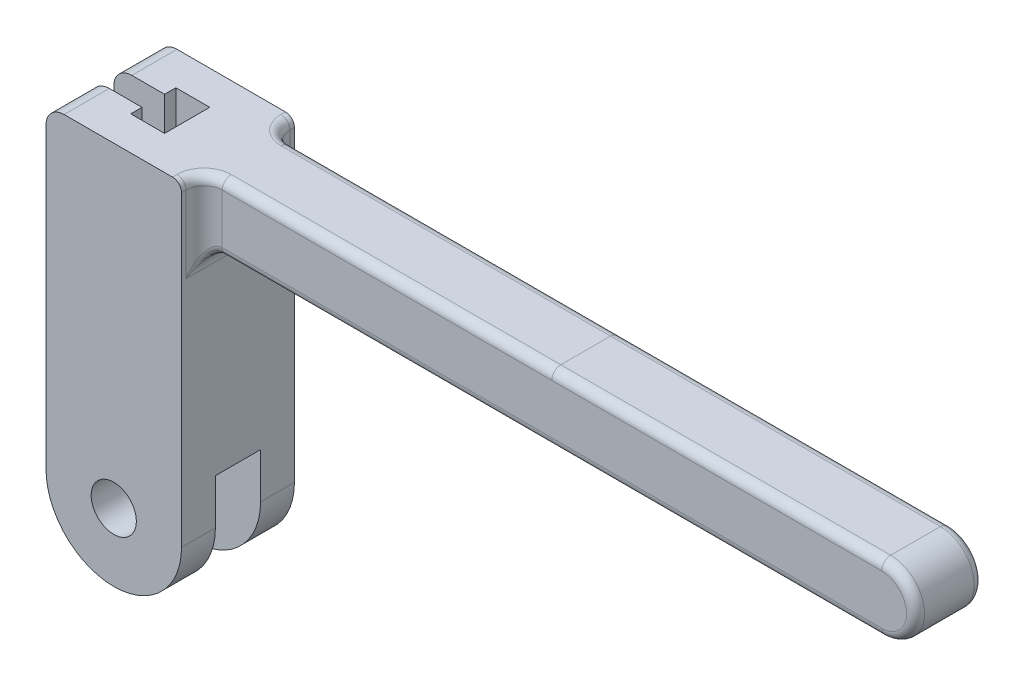
SolidWorks part; units mm, degrees
ref_plane "Front" through (0, 0, 0) normal (0, 0, 1) x (1, 0, 0)
ref_plane "Top" through (0, 0, 0) normal (0, 1, 0) x (1, 0, 0)
ref_plane "Right" through (0, 0, 0) normal (1, 0, 0) x (0, 0, -1)
sketch "Sketch1" plane through (0, 0, 0) normal (0, 0, 1) x (1, 0, 0)
  line L1 (12.065, 34.925) -> (104.775, 34.925)
  line L3 (104.775, 44.45) -> (-6.985, 44.45)
  line L4 (-9.525, 41.91) -> (-9.525, 0)
  line L5 (9.525, 0) -> (9.525, 32.385)
  arc A0 (-9.525, 0) -> (9.525, 0) centre (0, 0) ccw
  arc A1 (104.775, 34.925) -> (104.775, 44.45) centre (104.775, 39.6875) ccw
  arc A2 (9.525, 32.385) -> (12.065, 34.925) centre (12.065, 32.385) cw
  arc A3 (-6.985, 44.45) -> (-9.525, 41.91) centre (-6.985, 41.91) ccw
  circle A4 centre (0, 0) radius 3.175
  point P11 (9.525, 34.925)
  point P14 (-9.525, 44.45)
  dimension "D6" = 2.54
  dimension "D7" = 2.54
  dimension "D9" = 4.7625
  dimension "D10" = 9.525
  dimension "D11" = 6.35
  dimension "D1" = 19.05
  dimension "D2" = 9.525
  dimension "D3" = 44.45
  dimension "D4" = 34.925
  dimension "D5" = 114.3
  dimension "D8" = 104.775
extrude "Rough Shape Brake Lever" add sketch "Sketch1" along normal mid plane 15.875
sketch "Sketch3" plane through (9.525, 0, 0) normal (1, 0, 0) x (0, 0, -1)
  line L0 (-7.9375, 0) -> (-7.9375, 32.385) construction
  line L1 (-3.175, 6.35) -> (3.175, 6.35)
  line L2 (-3.175, 6.35) -> (-3.175, -12.0025)
  line L3 (-3.175, -12.0025) -> (3.175, -12.0025)
  line L4 (3.175, 6.35) -> (3.175, -12.0025)
  line L5 (-7.9375, 0) -> (7.9375, 0) construction
  dimension "D1" = 6.35
  dimension "D2" = 4.7625
  dimension "D3" = 6.35
extrude "Brake Lever Pivot Slot (Bottom)" cut sketch "Sketch3" against normal through all
sketch "Sketch5" plane through (0, 0, 7.9375) normal (0, 0, 1) x (1, 0, 0)
  line L0 (104.775, 44.45) -> (-6.985, 44.45) construction
  line L1 (9.525, 44.45) -> (120.3871, 44.45)
  line L2 (9.525, 44.45) -> (9.525, 29.21)
  line L3 (9.525, 29.21) -> (120.3871, 29.21)
  line L4 (120.3871, 44.45) -> (120.3871, 29.21)
  line L5 (9.525, 0) -> (9.525, 32.385) construction
  dimension "D1" = 0
  dimension "D2" = 110.8621
  dimension "D3" = 15.24
extrude "Brake Lever Width Cut (Front)" cut sketch "Sketch5" against normal blind 3.175
sketch "Sketch6" plane through (0, 0, -7.9375) normal (0, 0, -1) x (-1, 0, 0)
  line L0 (-9.525, 0) -> (-9.525, 32.385) construction
  line L1 (-9.525, 28.5022) -> (-117.1851, 28.5022)
  line L2 (-9.525, 28.5022) -> (-9.525, 47.5782)
  line L3 (-9.525, 47.5782) -> (-117.1851, 47.5782)
  line L4 (-117.1851, 28.5022) -> (-117.1851, 47.5782)
extrude "Brake Lever Width Cut (Back)" cut sketch "Sketch6" against normal blind 3.175
fillet "Brake Lever to Base Fillet 0.20-in" radius 2.54 2 edges at (9.525, 38.4175, -4.7625) (9.525, 38.4175, 4.7625)
sketch "Sketch7" plane through (0, 0, 0) normal (0, 0, 1) x (1, 0, 0)
  line L0 (9.525, 44.45) -> (-6.985, 44.45) construction
  circle A0 centre (0, 34.29) radius 2.3812
  dimension "D1" = 4.7625
  dimension "D2" = 10.16
extrude "Cylindrical Void Cut" cut sketch "Sketch7" against normal mid plane 6.35
sketch "Sketch9" plane through (0, 44.45, 0) normal (0, 1, 0) x (1, 0, 0)
  line L1 (-2.3813, 3.175) -> (2.3812, 3.175)
  line L2 (-2.3813, 3.175) -> (-2.3813, -3.175)
  line L3 (-2.3813, -3.175) -> (2.3813, -3.175)
  line L4 (2.3812, 3.175) -> (2.3813, -3.175)
  dimension "D1" = 6.35
  dimension "D2" = 3.175
  dimension "D3" = 4.7625
  dimension "D4" = 2.3813
extrude "Anchor Pocket Cut-Out" cut sketch "Sketch9" against normal up to next
sketch "Sketch10" plane through (-9.525, 0, 0) normal (-1, 0, 0) x (0, 0, 1)
  line L0 (7.9375, 44.45) -> (-7.9375, 44.45) construction
  line L1 (-1.5875, 46.99) -> (1.5875, 46.99)
  line L2 (-1.5875, 46.99) -> (-1.5875, 34.29)
  line L3 (-1.5875, 34.29) -> (1.5875, 34.29)
  line L4 (1.5875, 46.99) -> (1.5875, 34.29)
  line L5 (-7.9375, 41.91) -> (-7.9375, 0) construction
  dimension "D1" = 3.175
  dimension "D2" = 12.7
  dimension "D3" = 2.54
  dimension "D4" = 6.35
extrude "Cable Slot Cut-Out" cut sketch "Sketch10" against normal blind 9.525 contours L4 L3 L2 L1
sketch "Sketch11" plane through (-9.525, 0, 0) normal (-1, 0, 0) x (0, 0, 1)
  line L0 (-1.5875, 34.29) -> (1.5875, 34.29) construction
  line L1 (1.5875, 34.29) -> (-1.5875, 34.29)
  arc A0 (-1.5875, 34.29) -> (1.5875, 34.29) centre (0, 34.29) ccw
extrude "Cable Slot Bottom Round" cut sketch "Sketch11" against normal blind 9.525
ref_plane "Plane locates Split Line" through (58.4, 0, 0) normal (1, 0, 0) x (0, 0, -1)
split line "Split Line1-For Load Application"
fillet "Handle Fillet" radius 1.27 14 edges at (10.2689, 34.1811, -5.5064) (58.42, 34.925, -4.7625) (109.5375, 39.6875, -4.7625) (10.2689, 34.1811, 5.5064) (58.42, 34.925, 4.7625) (109.5375, 39.6875, 4.7625) (9.525, 44.45, 7.62) (81.5875, 44.45, -4.7625) (35.2325, 44.45, 4.7625) (9.525, 44.45, -7.62) (10.2689, 44.45, -5.5064) (10.2689, 44.45, 5.5064) (35.2325, 44.45, -4.7625) (81.5875, 44.45, 4.7625)
